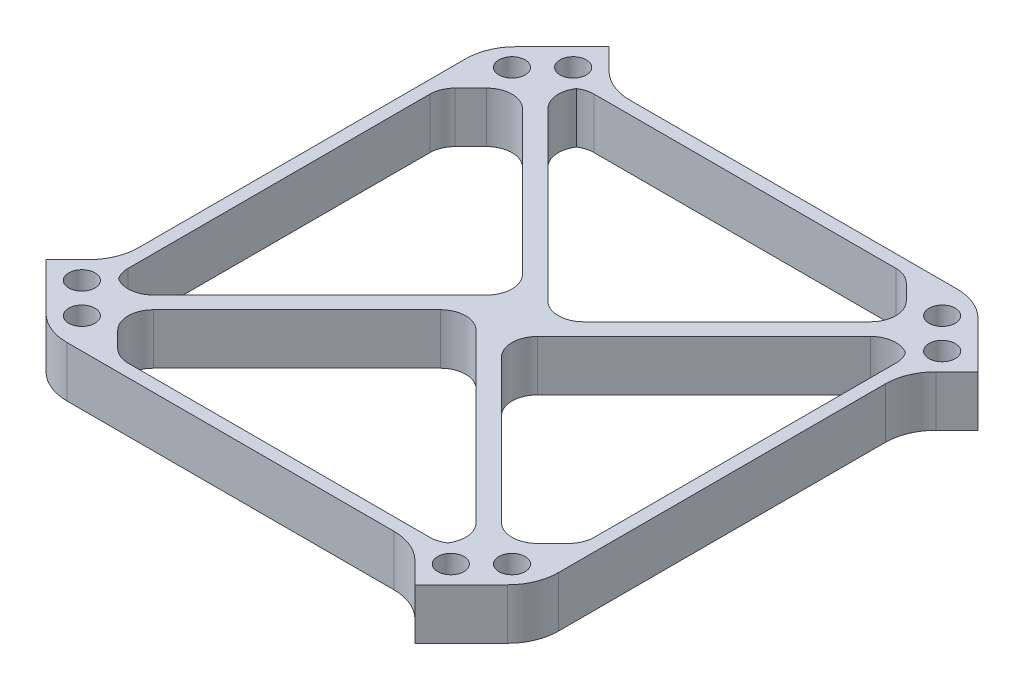
SolidWorks part; units mm, degrees
ref_plane "Front Plane" through (0, 0, 0) normal (0, 0, 1) x (1, 0, 0)
ref_plane "Top Plane" through (0, 0, 0) normal (0, 1, 0) x (1, 0, 0)
ref_plane "Right Plane" through (0, 0, 0) normal (1, 0, 0) x (0, 0, -1)
sketch "Sketch1" plane through (0, 0, 0) normal (0, 1, 0) x (1, 0, 0)
  line L0 (-55.533, 36.3909) -> (-36.3909, 55.533) construction
  line L1 (-36.3909, 55.533) -> (36.3909, 55.533) construction
  line L2 (36.3909, 55.533) -> (55.533, 36.3909) construction
  line L3 (55.533, 36.3909) -> (55.533, -36.3909) construction
  line L4 (55.533, -36.3909) -> (36.3909, -55.533) construction
  line L5 (36.3909, -55.533) -> (-36.3909, -55.533) construction
  line L6 (-36.3909, -55.533) -> (-55.533, -36.3909) construction
  line L7 (-55.533, -36.3909) -> (-55.533, 36.3909) construction
  line L8 (0, 0) -> (0, 31.0491) construction
  line L9 (0, 0) -> (32.6609, 0) construction
  line L10 (-48.4619, 43.4619) -> (-36.3909, 55.533)
  line L11 (-45.9619, -45.9619) -> (45.9619, -45.9619) construction
  line L12 (-45.9619, -45.9619) -> (-45.9619, 45.9619) construction
  line L13 (-45.9619, 45.9619) -> (45.9619, 45.9619) construction
  line L14 (45.9619, -45.9619) -> (45.9619, 45.9619) construction
  line L15 (-36.3909, 55.533) -> (-29.3198, 48.4619)
  line L16 (-29.3198, 48.4619) -> (43.4619, 48.4619)
  line L17 (43.4619, 48.4619) -> (55.533, 36.3909)
  line L18 (55.533, 36.3909) -> (48.4619, 29.3198)
  line L19 (48.4619, 29.3198) -> (48.4619, -43.4619)
  line L20 (48.4619, -43.4619) -> (36.3909, -55.533)
  line L21 (36.3909, -55.533) -> (29.3198, -48.4619)
  line L22 (29.3198, -48.4619) -> (-43.4619, -48.4619)
  line L23 (-43.4619, -48.4619) -> (-55.533, -36.3909)
  line L24 (-55.533, -36.3909) -> (-48.4619, -29.3198)
  line L25 (-48.4619, -29.3198) -> (-48.4619, 43.4619)
  point P18 (-45.9619, 45.9619)
  dimension "D1" = 65
  dimension "D2" = 10
  dimension "D3" = 2.5
extrude "Boss-Extrude1" add sketch "Sketch1" along normal blind 10
sketch "Sketch2" plane through (0, 10, 0) normal (0, 1, 0) x (1, 0, 0)
  line L0 (0, 0) -> (0, 27.7289) construction
  line L1 (48.4619, -48.4619) -> (-48.4619, -48.4619) construction
  line L2 (-48.4619, 43.4619) -> (-48.4619, -29.3198) construction
  line L3 (48.4619, 48.4619) -> (-48.4619, 48.4619) construction
  line L4 (-48.4619, -48.4619) -> (-48.4619, 48.4619) construction
  line L5 (0, 0) -> (26.129, 0) construction
  line L10 (-2.5, 4.5711) -> (-42.4264, -35.3553)
  line L11 (-45.9619, 31.8198) -> (-37.8553, 39.9264)
  line L12 (-37.8553, 39.9264) -> (-2.5, 4.5711)
  line L13 (-42.4264, -35.3553) -> (-45.9619, -31.8198)
  line L15 (43.4619, 48.4619) -> (-29.3198, 48.4619) construction
  line L16 (-43.4619, -48.4619) -> (29.3198, -48.4619) construction
  line L17 (48.4619, 48.4619) -> (48.4619, -48.4619) construction
  line L18 (48.4619, -43.4619) -> (48.4619, 29.3198) construction
  line L19 (-36.3909, 55.533) -> (-48.4619, 43.4619) construction
  line L20 (-45.9619, -31.8198) -> (-45.9619, 31.8198)
  line L21 (-48.4619, -29.3198) -> (-45.9619, -31.8198) construction
  dimension "D1" = 10
  dimension "D2" = 5
  dimension "D3" = 5
  dimension "D4" = 2.5
extrude "Cut-Extrude1" cut sketch "Sketch2" against normal through all
ref_axis "Axis2" through (0, 10.5, 0) along (0, -1, 0)
fillet "Fillet4" radius 5 5 edges at (-37.8553, 5, -39.9264) (-2.5, 5, -4.5711) (-45.9619, 5, 31.8198) (-42.4264, 5, 35.3553) (-45.9619, 5, -31.8198)
pattern_circular "CirPattern6" count 4 over 360 about axis through (0, 10.5, 0) along (0, -1, 0) of "Cut-Extrude1", "Fillet4"
fillet "Fillet5" radius 10 8 edges at (43.4619, 5, -48.4619) (-29.3198, 5, -48.4619) (-48.4619, 5, -43.4619) (-48.4619, 5, 29.3198) (-43.4619, 5, 48.4619) (29.3198, 5, 48.4619) (48.4619, 5, -29.3198) (48.4619, 5, 43.4619)
hole_wizard "#6 (0.204) Diameter Hole1" positions "Sketch3" profile "Sketch4" hole size "#6" standard "ANSI Inch" end condition through all
sketch "Sketch3" plane through (0, 10, 0) normal (0, 1, 0) x (1, 0, 0)
  line L1 (42.4264, -42.4264) -> (-42.4264, -42.4264) construction
  line L2 (42.4264, -42.4264) -> (42.4264, 42.4264) construction
  line L3 (42.4264, 42.4264) -> (-42.4264, 42.4264) construction
  line L4 (-42.4264, -42.4264) -> (-42.4264, 42.4264) construction
  line L5 (0, 0) -> (0, 27.9091) construction
  line L7 (0, 0) -> (26.5726, 0) construction
  line L9 (-36.3909, 55.533) -> (-45.533, 46.3909) construction
  line L11 (-43.4619, 48.4619) -> (-36.3909, 55.533) construction
  line L12 (-43.4619, 48.4619) -> (-36.3909, 41.3909) construction
  line L13 (-36.3909, 55.533) -> (-29.3198, 48.4619) construction
  line L16 (-36.3909, 41.3909) -> (-36.3909, 55.533) construction
  line L18 (-43.4619, 48.4619) -> (-29.3198, 48.4619) construction
  line L20 (-29.3198, 48.4619) -> (-36.3909, 41.3909) construction
  line L22 (-41.3909, 36.3909) -> (-44.4975, 33.2843) construction
  point P3 (-42.4264, 42.4264)
  point P355 (-36.3909, 48.4619)
  dimension "D1" = 5
  dimension "D2" = 60
sketch "Sketch4" plane through (-42.4264, 10, -42.4264) normal (1, 0, 0) x (0, 0, 1)
  line L0 (0, 0) -> (0, 10)
  line L1 (0, 10) -> (2.5908, 10)
  line L2 (2.5908, 10) -> (2.5908, 0)
  line L5 (2.5908, 0) -> (0, 0)
  line L11 (0, -6.35) -> (0, 107.95) construction
  dimension "Thru Hole Dia." = 5.1816
  dimension "Thru Hole Depth" = 10
pattern_circular "CirPattern7" count 4 over 360 about axis through (0, 10.5, 0) along (0, -1, 0) of "#6 (0.204) Diameter Hole1"
equation "\"TubeDiameter\" = 6.6929in"
